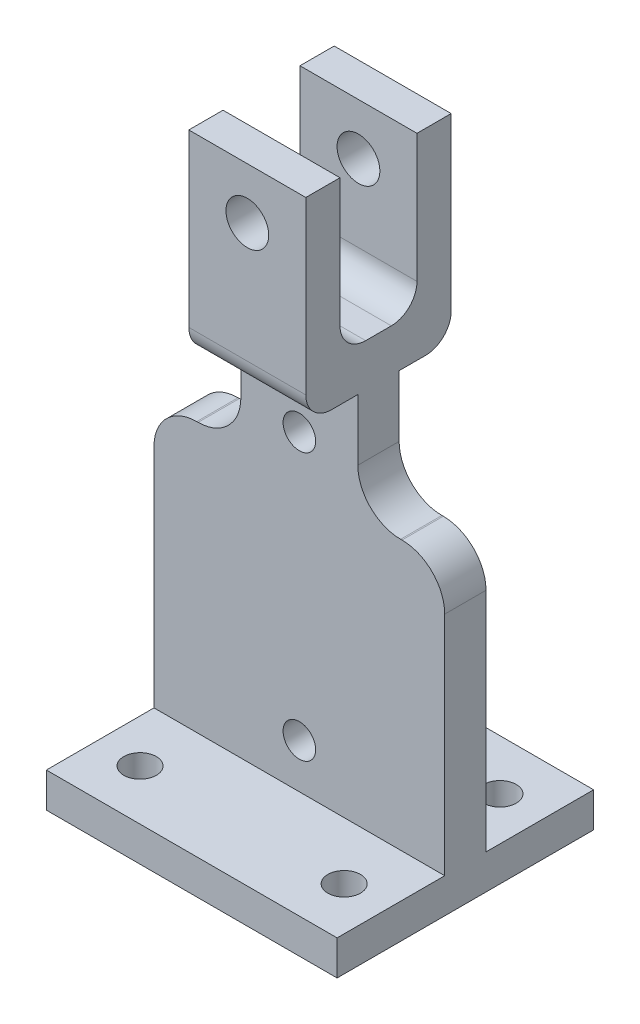
SolidWorks part; units mm, degrees
ref_plane "Front Plane" through (0, 0, 0) normal (0, 0, 1) x (1, 0, 0)
ref_plane "Top Plane" through (0, 0, 0) normal (0, 1, 0) x (1, 0, 0)
ref_plane "Right Plane" through (0, 0, 0) normal (1, 0, 0) x (0, 0, -1)
sketch "Sketch1" plane through (0, 0, 0) normal (0, 0, 1) x (1, 0, 0)
  line L0 (-17, 0) -> (17, 0)
  line L1 (17, 0) -> (17, 31.496)
  line L3 (6.84, 43.656) -> (-6.84, 43.656)
  line L4 (17, 31.496) -> (17, 43.656) construction
  line L5 (17, 43.656) -> (6.84, 43.656) construction
  line L6 (0, -55) -> (0, 55) construction
  line L7 (-17, 0) -> (-17, 31.496)
  line L9 (0, 0) -> (0, 5.207) construction
  line L10 (17, 31.496) -> (6.84, 31.496)
  line L11 (6.84, 31.496) -> (6.84, 43.656)
  line L12 (-6.84, 43.656) -> (-6.84, 31.496)
  line L13 (-6.84, 31.496) -> (-17.5151, 31.496)
  circle A0 centre (0, 5.207) radius 1.905
  circle A1 centre (0, 36.449) radius 1.905
  point P4 (0, 0)
  point P11 (0, 0)
  point P13 (0, 43.656)
  dimension "D5" = 3.81
  dimension "D7" = 2
  dimension "D1" = 34
  dimension "D2" = 43.656
  dimension "D3" = 12.16
  dimension "D4" = 10.16
  dimension "D6" = 5.207
  dimension "D8" = 7.207
extrude "Boss-Extrude1" add sketch "Sketch1" along normal mid plane 4.826 contours L12 L13 L7 L0 L1 L10 L11 L3 A1 A0 | L3 region at (0, 18.6426, 0)
sketch "Sketch3" plane through (0, 0, 0) normal (0, 1, 0) x (1, 0, 0)
  line L0 (0, 0) -> (-11.935, 0) construction
  line L1 (-17, -15) -> (17, -15)
  line L2 (-17, -15) -> (-17, 15)
  line L3 (-17, 15) -> (17, 15)
  line L4 (17, -15) -> (17, 15)
  line L5 (-17, -15) -> (17, 15) construction
  line L6 (-17, 15) -> (17, -15) construction
  line L7 (-11.935, 0) -> (-11.935, -9.11) construction
  line L8 (0, 0) -> (0, 8.8012) construction
  circle A0 centre (-11.935, -9.11) radius 1.905
  circle A1 centre (11.935, -9.11) radius 1.905
  circle A2 centre (11.935, 9.11) radius 1.905
  circle A3 centre (-11.935, 9.11) radius 1.905
  point P0 (0, 0)
  dimension "D5" = 3.81
  dimension "D1" = 34
  dimension "D2" = 30
  dimension "D3" = 11.935
  dimension "D4" = 9.11
  dimension "D6" = 2
  dimension "D7" = 2
extrude "Boss-Extrude2" add sketch "Sketch3" against normal blind 4.064
fillet "Fillet1" radius 5 4 edges at (-17, 31.496, 0) (17, 31.496, 0) (-6.84, 31.496, 0) (6.84, 31.496, 0)
sketch "Sketch5" plane through (0, 43.656, 0) normal (0, 1, 0) x (1, 0, 0)
  line L0 (-6.84, 8.5) -> (-6.84, -8.5)
  line L1 (-6.84, -8.5) -> (6.84, -8.5)
  line L2 (6.84, -8.5) -> (6.84, 8.5)
  line L3 (6.84, 8.5) -> (-6.84, 8.5)
  line L4 (-6.84, -2.413) -> (-6.84, 2.413) construction
  line L5 (6.84, -2.413) -> (6.84, 2.413) construction
  line L6 (-6.84, -4.5) -> (6.84, -4.5)
  line L7 (-6.84, 4.5) -> (6.84, 4.5)
  point P9 (6.84, 0)
  line M7 (6.84, 2.413) -> (-6.84, 2.413)
  line M8 (-6.84, 2.413) -> (-6.84, -2.413)
  line M9 (-6.84, -2.413) -> (6.84, -2.413)
  line M10 (6.84, -2.413) -> (6.84, 2.413)
  dimension "D1" = 17
  dimension "D2" = 8.5
  dimension "D3" = 4
  dimension "D4" = 4
extrude "Boss-Extrude4" add sketch "Sketch5" along normal blind 5 contours M10 M7 M8 M9 | L0 L6 L2 M9 | L7 L0 L2 M7 region at (0, 43.656, -3.4565) region at (0, 43.656, 0) region at (0, 43.656, 3.4565)
extrude "Boss-Extrude5" add sketch "Sketch5<3>" along normal blind 23 contours L6 L0 L1 L2 | L0 L7 L2 L3 region at (0, 43.656, -6.5) region at (0, 43.656, 6.5)
sketch "Sketch5<3>" plane through (0, 43.656, 0) normal (0, 1, 0) x (1, 0, 0) same geometry as "Sketch5"
sketch "Sketch6" plane through (0, 0, -8.5) normal (0, 0, -1) x (-1, 0, 0)
  line L0 (-6.84, 66.656) -> (6.84, 66.656) construction
  circle A0 centre (0, 60.656) radius 2.5
  point P4 (0, 66.656)
  dimension "D1" = 5
  dimension "D2" = 6
extrude "Cut-Extrude1" cut sketch "Sketch6" against normal up to surface (17 mm away) up to face at (0, 55.156, 8.5)
fillet "Fillet2" radius 3 4 edges at (0, 43.656, 8.5) (0, 48.656, 4.5) (0, 48.656, -4.5) (0, 43.656, -8.5)
